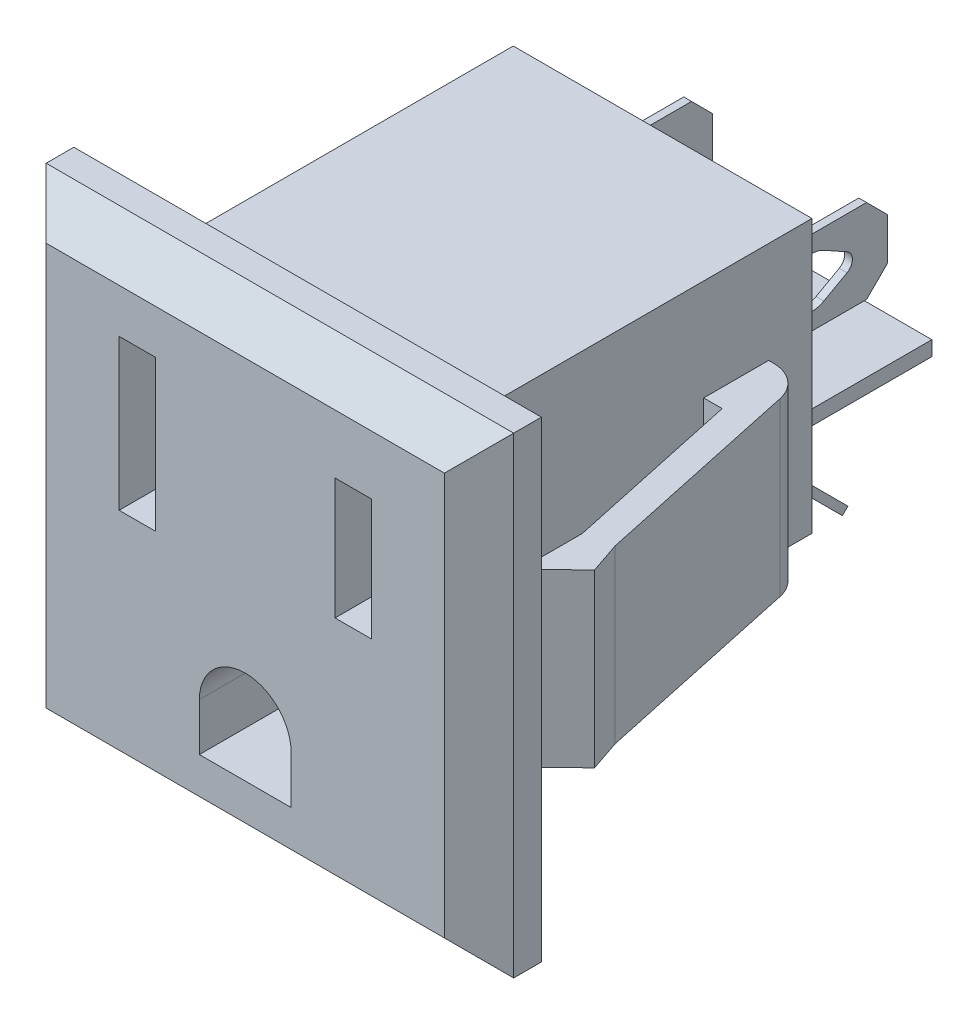
SolidWorks part; units mm, degrees
material "ABS"
ref_plane "Front Plane" through (0, 0, 0) normal (0, 0, 1) x (1, 0, 0)
ref_plane "Top Plane" through (0, 0, 0) normal (0, 1, 0) x (1, 0, 0)
ref_plane "Right Plane" through (0, 0, 0) normal (1, 0, 0) x (0, 0, -1)
sketch "Sketch1" plane through (0, 0, 0) normal (0, 0, 1) x (1, 0, 0)
  line L0 (-2.65, -6.775) -> (-2.65, -9.525)
  line L1 (-13.5, -13.625) -> (13.5, -13.625)
  line L2 (-13.5, -13.625) -> (-13.5, 13.625)
  line L3 (-13.5, 13.625) -> (13.5, 13.625)
  line L4 (13.5, -13.625) -> (13.5, 13.625)
  line L5 (0, 13.625) -> (0, -13.625) construction
  line L6 (-13.5, 0) -> (13.5, 0) construction
  line L7 (-2.65, -9.525) -> (2.65, -9.525)
  line L8 (2.65, -9.525) -> (2.65, -6.775)
  line L10 (-7.285, 9.075) -> (-5.185, 9.075)
  line L11 (-7.285, 9.075) -> (-7.285, 0.375)
  line L12 (-7.285, 0.375) -> (-5.185, 0.375)
  line L13 (-5.185, 9.075) -> (-5.185, 0.375)
  line L14 (-6.235, 0.375) -> (-6.235, 9.075) construction
  line L15 (-7.285, 4.725) -> (-5.185, 4.725) construction
  line L16 (5.185, 8.225) -> (7.285, 8.225)
  line L17 (5.185, 8.225) -> (5.185, 1.225)
  line L18 (5.185, 1.225) -> (7.285, 1.225)
  line L19 (7.285, 8.225) -> (7.285, 1.225)
  line L20 (6.235, 1.225) -> (6.235, 8.225) construction
  line L21 (5.185, 4.725) -> (7.285, 4.725) construction
  arc A0 (2.65, -6.775) -> (-2.65, -6.775) centre (0, -6.775) ccw
  point P0 (0, 0)
  point P22 (0, 0)
  point P23 (-4.769, 9.075)
  point P24 (0, 0)
  point P25 (0, -4.125)
  point P131 (-6.235, 4.725)
  point P188 (6.235, 4.725)
  dimension "D6" = 2.65
  dimension "D1" = 27.25
  dimension "D2" = 27
  dimension "D3" = 2.1
  dimension "D4" = 8.7
  dimension "D5" = 4.55
  dimension "D7" = 2.1
  dimension "D8" = 7
  dimension "D9" = 10.37
  dimension "D10" = 5.4
  dimension "D11" = 4.1
extrude "Boss-Extrude1" add sketch "Sketch1" along normal blind 3.6 contours L3 L4 L1 L2
chamfer "Chamfer1" distance 2 angle 45 4 edges at (13.5, 0, 3.6) (0, -13.625, 3.6) (-13.5, 0, 3.6) (0, 13.625, 3.6)
sketch "Sketch2" plane through (0, 0, 0) normal (0, 0, -1) x (-1, 0, 0)
  line L0 (0, 13.625) -> (0, -13.625) construction
  line L1 (-13.5, 13.625) -> (13.5, 13.625) construction
  line L2 (13.5, -13.625) -> (-13.5, -13.625) construction
  line L3 (-8.625, 10.875) -> (8.625, 10.875)
  line L4 (-8.625, 10.875) -> (-8.625, -4.875)
  line L5 (-8.625, -4.875) -> (-4.325, -4.875)
  line L6 (-4.325, -4.875) -> (-4.325, -11.025)
  line L7 (4.325, -4.875) -> (4.325, -11.025)
  line L8 (8.625, -4.875) -> (4.325, -4.875)
  line L9 (8.625, 10.875) -> (8.625, -4.875)
  line L10 (-4.325, -11.025) -> (4.325, -11.025)
  point P9 (0, 10.875)
  dimension "D1" = 17.25
  dimension "D2" = 21.9
  dimension "D3" = 8.65
  dimension "D4" = 6.15
  dimension "D5" = 2.75
extrude "Boss-Extrude2" add sketch "Sketch2" along normal blind 20.5
extrude "Cut-Extrude1" cut sketch "Sketch1<3>" against normal blind 22 from surface contours L13 L10 L11 L12 | L19 L16 L17 L18 | L8 A0 L0 L7 region at (0, -7.0731, 0) region at (-6.235, 4.725, 0) region at (6.235, 4.725, 0) starting at face at (0, 0, 3.6)
sketch "Sketch1<3>" plane through (0, 0, 0) normal (0, 0, 1) x (1, 0, 0) same geometry as "Sketch1"
sketch "Sketch3" plane through (0, 0, -20.5) normal (0, 0, -1) x (-1, 0, 0)
  line L0 (0, 10.875) -> (0, -11.025) construction
  line L1 (-5.28, 9.125) -> (-4.83, 9.125)
  line L2 (-5.28, 9.125) -> (-5.28, -0.475)
  line L3 (-5.28, -0.475) -> (-4.83, -0.475)
  line L4 (-4.83, 9.125) -> (-4.83, -0.475)
  line L5 (-5.055, -0.475) -> (-5.055, 9.125) construction
  line L6 (-5.28, 4.325) -> (-4.83, 4.325) construction
  line L7 (8.625, 10.875) -> (-8.625, 10.875) construction
  line L8 (-4.325, -11.025) -> (4.325, -11.025) construction
  line L9 (5.28, -0.475) -> (4.83, -0.475)
  line L10 (5.28, 9.125) -> (4.83, 9.125)
  line L11 (4.83, 9.125) -> (4.83, -0.475)
  line L12 (5.28, 9.125) -> (5.28, -0.475)
  line L14 (-4.8, -4.075) -> (4.8, -4.075)
  line L15 (-4.8, -4.075) -> (-4.8, -4.525)
  line L16 (-4.8, -4.525) -> (4.8, -4.525)
  line L17 (4.8, -4.075) -> (4.8, -4.525)
  line L18 (0, -4.525) -> (0, -4.075) construction
  line L19 (-4.8, -4.3) -> (4.8, -4.3) construction
  point P16 (0, -4.3)
  point P152 (-5.055, 4.325)
  dimension "D1" = 9.6
  dimension "D2" = 1.75
  dimension "D3" = 9.66
  dimension "D4" = 0.45
  dimension "D5" = 6.5
extrude "Boss-Extrude3" add sketch "Sketch3" along normal blind 1.6 contours L4 L1 L2 L3 | L12 L10 L11 L9 | L17 L14 L15 L16 region at (5.055, 4.325, -20.5) region at (-5.055, 4.325, -20.5) region at (0, -4.3, -20.5)
chamfer "Chamfer2" distance 1.5 angle 45 4 edges at (-5.055, -0.475, -22.1) (-5.055, 9.125, -22.1) (5.055, 9.125, -22.1) (5.055, -0.475, -22.1)
sketch "Sketch4" plane through (0, 0, -22.1) normal (0, 0, -1) x (-1, 0, 0)
  line L0 (-5.055, 9.125) -> (-5.055, -0.475) construction
  line L1 (-5.28, 9.125) -> (-4.83, 9.125) construction
  line L2 (-4.83, -0.475) -> (-5.28, -0.475) construction
  line L3 (5.055, 9.125) -> (5.055, -0.475) construction
  line L4 (4.83, 9.125) -> (5.28, 9.125) construction
  line L5 (5.28, -0.475) -> (4.83, -0.475) construction
  line L6 (-4.83, 7.625) -> (-4.83, 1.025) construction
  line L7 (-5.28, 1.9) -> (-4.83, 1.9)
  line L8 (-5.28, 1.9) -> (-5.28, 6.75)
  line L9 (-5.28, 6.75) -> (-4.83, 6.75)
  line L10 (-4.83, 1.9) -> (-4.83, 6.75)
  line L11 (-5.055, 6.75) -> (-5.055, 1.9) construction
  line L12 (-5.28, 4.325) -> (-4.83, 4.325) construction
  line L13 (0, 0) -> (0, 7.2065) construction
  line L14 (5.28, 1.9) -> (4.83, 1.9)
  line L15 (4.83, 1.9) -> (4.83, 6.75)
  line L16 (5.28, 1.9) -> (5.28, 6.75)
  line L17 (5.28, 6.75) -> (4.83, 6.75)
  point P12 (-5.055, 4.325)
  point P27 (-5.055, 4.325)
  dimension "D1" = 4.85
extrude "Boss-Extrude4" add sketch "Sketch4" along normal blind 6.1
sketch "Sketch5" plane through (0, 0, 0) normal (1, 0, 0) x (0, 0, -1)
  line L0 (22.1, -4.075) -> (29.65, -11.625)
  line L1 (29.65, -11.625) -> (29.3318, -11.9432)
  line L2 (29.3318, -11.9432) -> (21.9136, -4.525)
  line L3 (22.1, -4.525) -> (20.5, -4.525) construction
  line L4 (21.9136, -4.525) -> (22.1, -4.525)
  line L5 (22.1, -4.525) -> (22.1, -4.075)
  line L6 (21.9136, -4.525) -> (21.9136, -4.075) construction
  line L7 (22.1, -4.075) -> (20.5, -4.075) construction
  line L8 (20.5, -4.875) -> (20.5, -11.025) construction
  dimension "D1" = 135
  dimension "D2" = 9.15
extrude "Boss-Extrude5" add sketch "Sketch5" along normal mid plane 4.8
sketch "Sketch6" plane through (0, 0, -20.5) normal (0, 0, -1) x (-1, 0, 0)
  line L0 (8.625, 10.875) -> (-8.625, 10.875) construction
  line L1 (-6.6, -0.675) -> (6.6, -0.675)
  line L2 (-6.6, -0.675) -> (-6.6, -1.525)
  line L3 (-6.6, -1.525) -> (6.6, -1.525)
  line L4 (6.6, -0.675) -> (6.6, -1.525)
  line L5 (0, -1.525) -> (0, -0.675) construction
  line L6 (-6.6, -1.1) -> (6.6, -1.1) construction
  point P0 (0, -1.1)
  dimension "D1" = 0.85
  dimension "D2" = 13.2
  dimension "D3" = 12.4
extrude "Boss-Extrude6" add sketch "Sketch6" along normal blind 8.95
chamfer "Chamfer3" distance 1.2 angle 45 6 edges at (-2.4, -11.7841, -29.4909) (2.4, -11.7841, -29.4909) (-5.055, 1.9, -28.2) (-5.055, 6.75, -28.2) (5.055, 1.9, -28.2) (5.055, 6.75, -28.2)
sketch "Sketch7" plane through (5.28, 0, 0) normal (1, 0, 0) x (0, 0, -1)
  line L0 (28.2, 4.325) -> (23.83, 4.325) construction
  line L1 (28.2, 5.55) -> (28.2, 3.1) construction
  line L2 (24.5343, 5.5925) -> (25.8714, 4.8495)
  line L3 (24.5343, 3.0575) -> (25.8714, 3.8005)
  arc A0 (24.5343, 5.5925) -> (24.5343, 3.0575) centre (23.83, 4.325) ccw
  arc A1 (25.8714, 3.8005) -> (25.8714, 4.8495) centre (25.58, 4.325) ccw
  point P4 (22.38, 4.325)
  point P6 (26.18, 4.325)
  dimension "D1" = 3.8
  dimension "D2" = 1.45
  dimension "D3" = 0.6
  dimension "D4" = 2.02
extrude "Cut-Extrude2" cut sketch "Sketch7" against normal through all
sketch "Sketch8" plane through (0, 9.0125, -9.0125) normal (0, 0.7071, -0.7071) x (1, 0, 0)
  line L0 (0, 29.1858) -> (0, 24.8158) construction
  line L1 (1.2, 29.1858) -> (-1.2, 29.1858) construction
  line L2 (-0.5245, 26.8573) -> (-1.2675, 25.5201)
  line L3 (0.5245, 26.8573) -> (1.2675, 25.5201)
  arc A0 (-1.2675, 25.5201) -> (1.2675, 25.5201) centre (0, 24.8158) ccw
  arc A1 (0.5245, 26.8573) -> (-0.5245, 26.8573) centre (0, 26.5658) ccw
  point P5 (0, 27.1658)
  point P7 (0, 23.3658)
  point P12 (0, 0)
  point P13 (0, 27.1658)
  dimension "D1" = 3.8
  dimension "D2" = 1.45
  dimension "D3" = 0.6
  dimension "D4" = 2.02
extrude "Cut-Extrude3" cut sketch "Sketch8" against normal up to next
sketch "Sketch9" plane through (0, -4.875, 0) normal (0, -1, 0) x (1, 0, 0)
  line L0 (-8.625, -18) -> (-10.525, -18)
  line L1 (-8.625, -20.5) -> (-8.625, 0) construction
  line L2 (-10.525, -18) -> (-13.4644, -4.2992)
  line L3 (-13.4644, -4.2992) -> (-14.075, -2.5)
  line L4 (-14.075, -2.5) -> (-11.9, -0.36)
  line L5 (-11.9, -0.36) -> (-11.9, -3.9636)
  line L6 (-11.9, -3.9636) -> (-9.6931, -14.25)
  line L7 (-9.6931, -14.25) -> (-8.625, -14.25)
  line L8 (-8.625, -14.25) -> (-8.625, -18)
  line L9 (-13.5, 0) -> (13.5, 0) construction
  line L10 (-13.4644, -4.2992) -> (-11.9, -3.9636) construction
  point P4 (0, 0)
  point P11 (-14.075, -2.5009)
  dimension "D1" = 2.5
  dimension "D2" = 3.75
  dimension "D3" = 1.6
  dimension "D4" = 0.36
  dimension "D5" = 2.5
  dimension "D7" = 1.9
  dimension "D9" = 14.075
  dimension "D10" = 1.9
  dimension "D11" = 11.9
extrude "Boss-Extrude7" add sketch "Sketch9" against normal blind 9.9
mirror "Mirror1" about plane through (0, 0, 0) normal (1, 0, 0) of "Boss-Extrude7"
fillet "Fillet1" radius 2 2 edges at (10.525, 0.075, -18) (-10.525, 0.075, -18)
sketch "Sketch10"
sketch_block_instance "Block1-1"
sketch_block "Block1" parameters "D1"=24.5
equation "\"D7@Sketch1\"=\"D3@Sketch1\""
